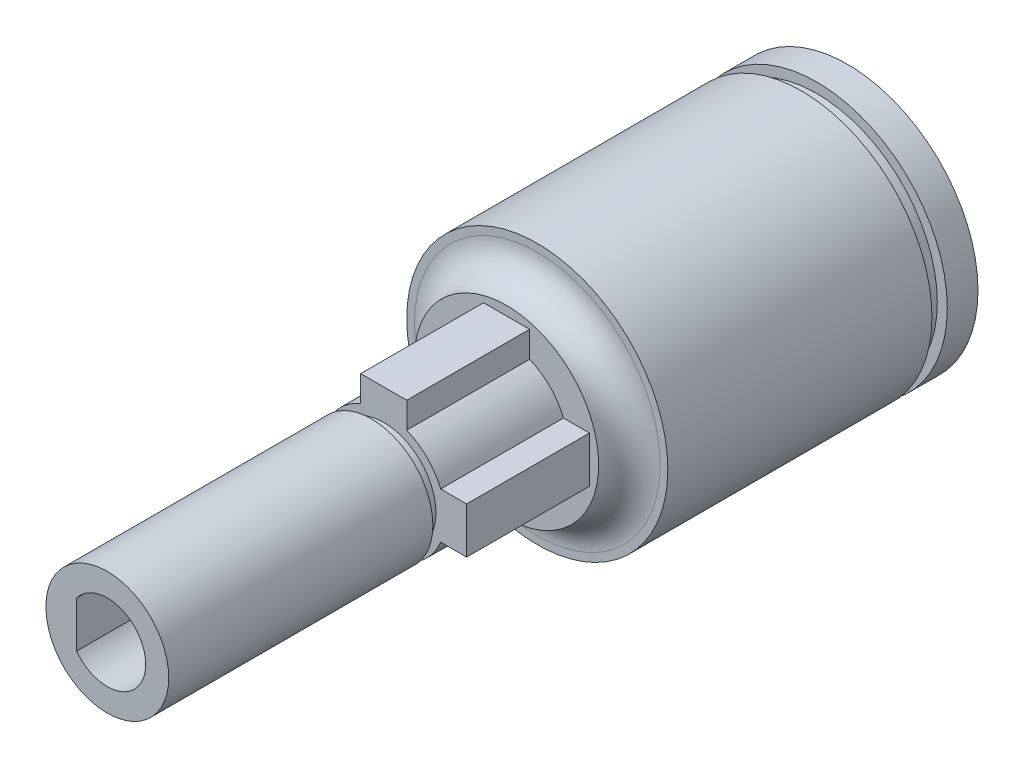
SolidWorks part; units mm, degrees
note: The reader was unsure of these and kept them because the rebuilt part matched: shared geometry of "草图1<3>", "草图2<3>".
ref_plane "前视基准面" through (0, 0, 0) normal (0, 0, 1) x (1, 0, 0)
ref_plane "上视基准面" through (0, 0, 0) normal (0, 1, 0) x (1, 0, 0)
ref_plane "右视基准面" through (0, 0, 0) normal (1, 0, 0) x (0, 0, -1)
sketch "草图1" plane through (0, 0, 0) normal (0, 0, 1) x (1, 0, 0)
  line L1 (-2, 0) -> (-2, 1.5)
  line L2 (-2, 0) -> (-2, -1.5)
  line L12 (3.7081, -1.5) -> (5.4, -1.5)
  line L13 (-1.5, 5.4) -> (-1.5, 3.7081)
  line L14 (1.5, 5.4) -> (-1.5, 5.4)
  line L15 (1.5, 3.7081) -> (1.5, 5.4)
  line L16 (5.4, 1.5) -> (3.7081, 1.5)
  line L17 (5.4, -1.5) -> (5.4, 1.5)
  circle A0 centre (0, 0) radius 2.5
  arc A1 (-1.5, 3.7081) -> (1.5, 3.7081) centre (0, 0) cw
  arc A2 (3.7081, 1.5) -> (3.7081, -1.5) centre (0, 0) cw
  arc A4 (-1.5, 3.7081) -> (3.7081, -1.5) centre (0, 0) ccw
  arc A5 (3.7081, 1.5) -> (1.5, 3.7081) centre (0, 0) ccw
extrude "凸台-拉伸1" add sketch "草图1" along normal blind 25 and the other way blind 1 contours L16 A5 L15 L14 L13 A4 L12 L17 A0 | L1 A0 L2
extrude "凸台-拉伸2" add sketch "草图1<3>" along normal blind 7 and the other way blind 1 contours L13 A1 L15 L14 | L16 A2 L12 L17
sketch "草图1<3>" plane through (0, 0, 0) normal (0, 0, 1) x (1, 0, 0) same geometry as "草图1"
ref_plane "基准面1" through (0, 0, -1) normal (0, 0, -1) x (-1, 0, 0)
sketch "草图2" plane through (0, 0, -1) normal (0, 0, -1) x (-1, 0, 0)
  circle A0 centre (0, 0) radius 6
  circle A1 centre (0, 0) radius 2.5
extrude "凸台-拉伸3" add sketch "草图2" against normal blind 2 contours A1
extrude "凸台-拉伸4" add sketch "草图2<3>" along normal blind 2 contours A1 | A0 A1
sketch "草图2<3>" plane through (0, 0, -1) normal (0, 0, -1) x (-1, 0, 0) same geometry as "草图2"
ref_plane "基准面2" through (0, 0, 7) normal (0, 0, 1) x (1, 0, 0)
sketch "草图4" plane through (0, 0, 0) normal (1, 0, 0) x (0, 0, -1)
  line L0 (-7.8, 4) -> (-7.8, 3.4)
  line L1 (-7, 4) -> (-7.8, 4)
  line L2 (-7.8, 3.4) -> (-7, 3.4)
  line L3 (-7, 3.4) -> (-7, 4)
  line L4 (0, 0) -> (-4.7, 0) construction
revolve "切除-旋转3" cut sketch "草图4" angle 360 about L4
ref_plane "基准面3" through (0, 0, -3) normal (0, 0, -1) x (-1, 0, 0)
sketch "草图5" plane through (0, 0, -3) normal (0, 0, -1) x (-1, 0, 0)
  circle A0 centre (0, 0) radius 8.5
extrude "凸台-拉伸5" add sketch "草图5" along normal blind 20.2
sketch "草图6" plane through (0, 0, 0) normal (1, 0, 0) x (0, 0, -1)
  line L0 (0, 0) -> (19, 0) construction
  line L3 (20.2, 7.85) -> (20.2, 8.5)
  line L4 (20.2, 8.5) -> (21.2, 8.5)
  line L5 (21.2, 8.5) -> (21.2, 7.85)
  line L6 (21.2, 7.85) -> (20.2, 7.85)
revolve "切除-旋转4" cut sketch "草图6" angle 360 about L0
fillet "圆角2" radius 2 1 edges at (-6, 0, -3)
